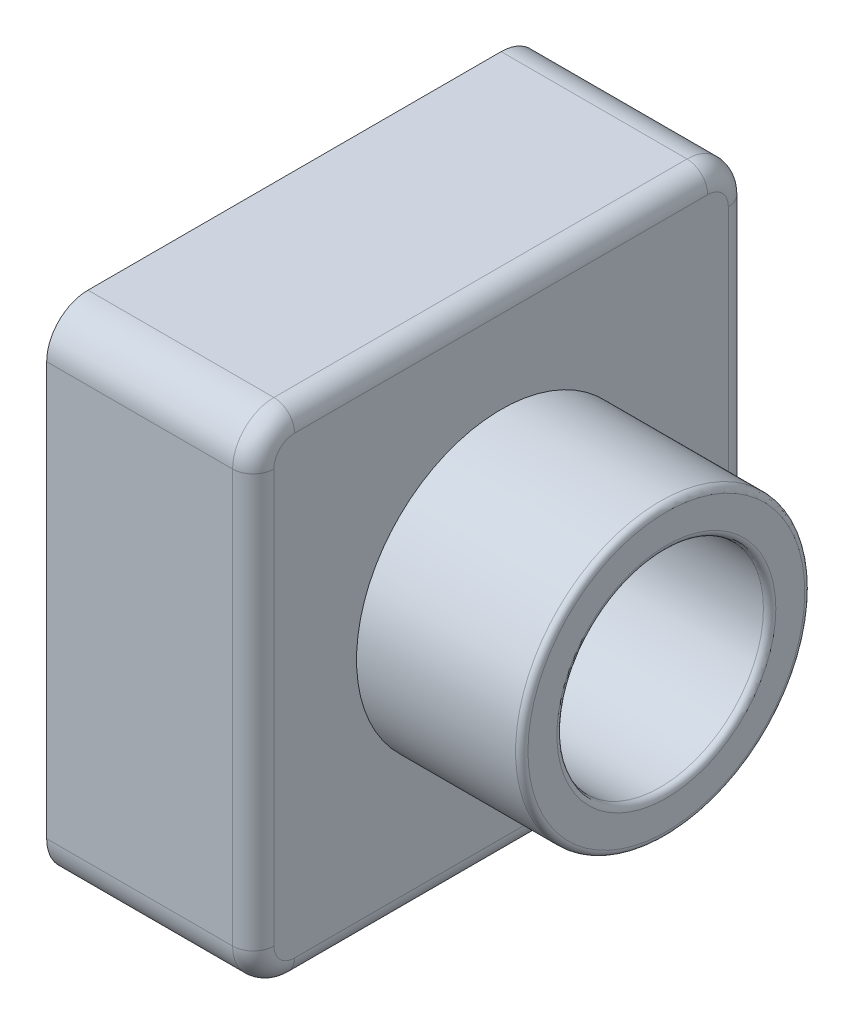
SolidWorks part; units mm, degrees
material "Plain Carbon Steel"
ref_plane "Front Plane" through (0, 0, 0) normal (0, 0, 1) x (1, 0, 0)
ref_plane "Top Plane" through (0, 0, 0) normal (0, 1, 0) x (1, 0, 0)
ref_plane "Right Plane" through (0, 0, 0) normal (1, 0, 0) x (0, 0, -1)
sketch "Sketch1" plane through (0, 0, 0) normal (1, 0, 0) x (0, 0, -1)
  line L1 (0, 0) -> (-120, 0)
  line L2 (0, 0) -> (0, 120)
  line L3 (0, 120) -> (-120, 120)
  line L4 (-120, 0) -> (-120, 120)
  dimension "D1" = 120
  dimension "D2" = 120
extrude "Boss-Extrude1" add sketch "Sketch1" along normal blind 50
sketch "Sketch2" plane through (50, 0, 0) normal (1, 0, 0) x (0, 0, -1)
  line L0 (0, 120) -> (-120, 120) construction
  line L1 (0, 0) -> (0, 120) construction
  circle A0 centre (-60, 60) radius 35
  dimension "D1" = 70
  dimension "D2" = 60
  dimension "D3" = 60
extrude "Boss-Extrude2" add sketch "Sketch2" along normal blind 40
sketch "Sketch4" plane through (90, 0, 0) normal (1, 0, 0) x (0, 0, -1)
  circle A2 centre (-60, 60) radius 25
  circle A4 centre (-60, 60) radius 25
  dimension "D1" = 10
extrude "Cut-Extrude2" cut sketch "Sketch4" against normal through all
sketch "Sketch3" plane through (90, 0, 0) normal (1, 0, 0) x (0, 0, -1)
  circle A0 centre (-60, 60) radius 25
  dimension "D1" = 50
extrude "Cut-Extrude1" cut sketch "Sketch3" against normal through all both and the other way through all
fillet "Fillet2" radius 10 4 edges at (25, 0, 0) (25, 0, 120) (25, 120, 120) (25, 120, 0)
fillet "Fillet3" radius 1.5 2 edges at (90, 60, 25) (90, 60, 35)
fillet "Fillet5" radius 5 9 edges at (50, 2.9289, 117.0711) (50, 60, 120) (50, 117.0711, 117.0711) (50, 120, 60) (50, 117.0711, 2.9289) (50, 60, 0) (50, 2.9289, 2.9289) (50, 0, 60) (50, 60, 35)
shell "Shell1" thickness 2 removed face at (0, 60, 35)
